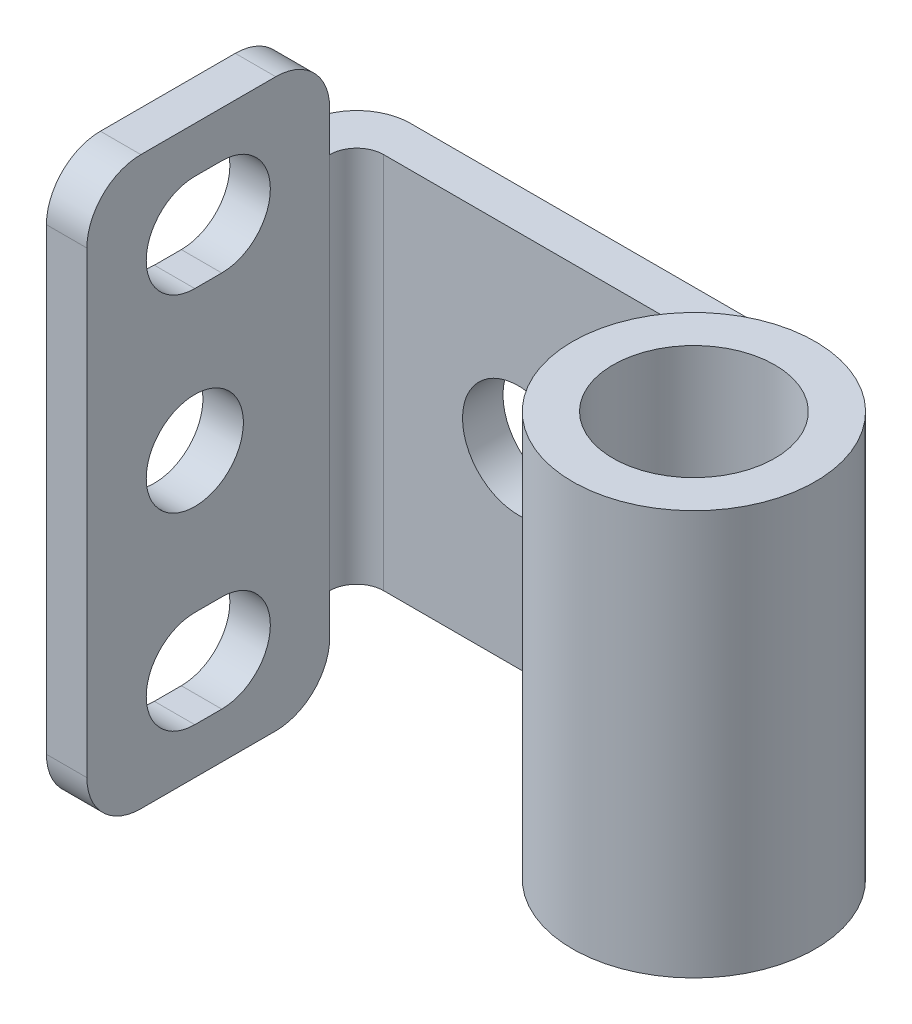
SolidWorks part; units mm, degrees
ref_plane "Спереди" through (0, 0, 0) normal (0, 0, 1) x (1, 0, 0)
ref_plane "Сверху" through (0, 0, 0) normal (0, 1, 0) x (1, 0, 0)
ref_plane "Справа" through (0, 0, 0) normal (1, 0, 0) x (0, 0, -1)
sketch "Эскиз1" plane through (0, 0, 0) normal (0, 0, 1) x (1, 0, 0)
  line L1 (0, 0) -> (11, 0)
  line L2 (0, 0) -> (0, -14)
  line L3 (0, -14) -> (11, -14)
  line L4 (11, 0) -> (11, -14)
  dimension "D1" = 11
  dimension "D2" = 14
base flange "Базовая кромка1" sketch "Эскиз1" thickness 1.5 reverse thickness direction no parameters "D1"=1.7
ref_plane "Плоскость4" through (0, -14.5, 0) normal (0, -1, 0) x (-1, 0, 0)
sketch "Эскиз9" plane through (0, -14.5, 0) normal (0, -1, 0) x (-1, 0, 0)
  line L0 (-4.9522, 1.5) -> (-14.4314, 1.5) construction
  line L1 (0, 1.5) -> (-11, 1.5) construction
  line L2 (-11, 0) -> (-11, -7.4344) construction
  circle A0 centre (-15.5, -3) radius 3
  dimension "D1" = 6
  dimension "D2" = 4.5
  dimension "D3" = 4.5
extrude "Вытянуть-Тонкостенный1" add sketch "Эскиз9" against normal blind 15 separate body thin thin type one direction wall 1.5
sketch "Эскиз10" plane through (11, 0, 0) normal (1, 0, 0) x (0, 0, -1)
  line L0 (0, -14) -> (0, 0) construction
  line L1 (1.5, 0) -> (0, 0)
  line L2 (1.5, 0) -> (1.5, -14)
  line L3 (1.5, -14) -> (0, -14)
  line L4 (0, 0) -> (0, -14)
  line L5 (1.5, -14) -> (0, -14) construction
extrude "Бобышка-Вытянуть1" add sketch "Эскиз10" along normal blind 4.5
sketch "Эскиз11" plane through (0, 0, -1.5) normal (0, 0, -1) x (-1, 0, 0)
  line L1 (0, -14) -> (1.5, -14)
  line L2 (0, -14) -> (0, 0)
  line L3 (0, 0) -> (1.5, 0)
  line L4 (1.5, -14) -> (1.5, 0)
  dimension "D1" = 1.5
extrude "Бобышка-Вытянуть2" add sketch "Эскиз11" against normal blind 11.5
fillet "Скругление2" radius 2 1 edges at (-1.5, -7, -1.5)
fillet "Скругление3" radius 1 1 edges at (0, -7, 0)
sketch "Эскиз12" plane through (-1.5, 0, 0) normal (-1, 0, 0) x (0, 0, 1)
  line L0 (10, -7) -> (-5.3539, -7) construction
  line L1 (10, -14) -> (1, -14)
  line L2 (10, -14) -> (10, -17.5)
  line L3 (10, -17.5) -> (1, -17.5)
  line L4 (1, -14) -> (1, -17.5)
  line L5 (10, -14) -> (10, 0) construction
  line L6 (10, 3.5) -> (1, 3.5)
  line L7 (1, 0) -> (1, 3.5)
  line L8 (10, 0) -> (1, 0)
  line L9 (10, 0) -> (10, 3.5)
  dimension "D1" = 3.5
  dimension "D2" = 9
extrude "Бобышка-Вытянуть3" add sketch "Эскиз12" against normal blind 1.5
fillet "Скругление4" radius 2 4 edges at (-0.75, 3.5, 10) (-0.75, 3.5, 1) (-0.75, -17.5, 1) (-0.75, -17.5, 10)
sketch "Эскиз13" plane through (-1.5, 0, 0) normal (-1, 0, 0) x (0, 0, 1)
  line L0 (5.5, 3.5) -> (5.5, -17.5) construction
  line L1 (8, 3.5) -> (3, 3.5) construction
  line L2 (3, -17.5) -> (8, -17.5) construction
  line L3 (10, -7) -> (0.5, -7) construction
  line L4 (10, -15.5) -> (10, 1.5) construction
  line L5 (0.5, 0) -> (0.5, -14) construction
  line L6 (5, 0) -> (6, 0) construction
  line L7 (5, 1.8) -> (6, 1.8)
  line L8 (5, -1.8) -> (6, -1.8)
  line L9 (5, -14) -> (6, -14) construction
  line L10 (5, -15.8) -> (6, -15.8)
  line L11 (5, -12.2) -> (6, -12.2)
  arc A0 (5, 1.8) -> (5, -1.8) centre (5, 0) ccw
  arc A1 (6, -1.8) -> (6, 1.8) centre (6, 0) ccw
  arc A2 (5, -15.8) -> (5, -12.2) centre (5, -14) cw
  arc A3 (6, -12.2) -> (6, -15.8) centre (6, -14) cw
  circle A4 centre (6, -7) radius 1.8
  point P15 (5.5, 0)
  point P23 (5.5, -14)
  dimension "D2" = 1.8
  dimension "D3" = 3.6
  dimension "D1" = 1
extrude "Вырез-Вытянуть1" cut sketch "Эскиз13" against normal blind 1.5 normal cut yes
sketch "Эскиз14" plane through (0, 0, -1.5) normal (0, 0, -1) x (-1, 0, 0)
  line L0 (-0.5, -7) -> (-15.5, -7) construction
  line L1 (-0.5, -14) -> (-0.5, 0) construction
  line L2 (-15.5, -14) -> (-15.5, 0) construction
  circle A0 centre (-6, -7) radius 2.0766
  point P8 (-7.075, -7.5)
  dimension "D1" = 9.5
extrude "Вырез-Вытянуть2" cut sketch "Эскиз14" against normal blind 1.5 normal cut yes
sketch "Сгиб-Линии1" [suppressed] plane through (0, 0, 0) normal (0, 1, 0) x (1, 0, 0)
sketch "Граничная рамка1" [suppressed] plane through (0, 0, 0) normal (0, 1, 0) x (1, 0, 0)
sheet metal parameters "Листовой металл1" thickness 1.5 parameters "D1"=1.7
flat pattern "Развертка1" [suppressed]
sketch "Сгиб-Линии2" plane through (0, 0, 0) normal (0, 1, 0) x (1, 0, 0)
sketch3d "Граничная рамка2" [suppressed]
  line L0 (-7.5, 0, 0) -> (-7.5, -11, 0) construction
  line L1 (0, 0, 0) -> (0, -11, 0) construction
  line L2 (-7.5, 0, 0) -> (0, 0, 0) construction
  line L3 (-7.5, -11, 0) -> (0, -11, 0) construction
sheet metal parameters "Листовой металл4" thickness 1.5 parameters "D1"=1.7
flat pattern "Развертка1"
sketch "Сгиб-Линии2" plane through (0, 0, 0) normal (0, 0, 1) x (1, 0, 0)
  point P0 (1.3402, 0)
  point P1 (1.3402, -15)
sketch3d "Граничная рамка2" [suppressed]
  line L0 (12.1459, 0, 0) -> (12.1459, -15, 0) construction
  line L1 (0, 0, 0) -> (0, -15, 0) construction
  line L2 (12.1459, 0, 0) -> (0, 0, 0) construction
  line L3 (12.1459, -15, 0) -> (0, -15, 0) construction
sheet metal parameters "Листовой металл5" thickness 1.5 parameters "D1"=1.7
flat pattern "Развертка1"
sketch "Сгиб-Линии2" plane through (0, 0, 0) normal (0, 0, 1) x (1, 0, 0)
sketch3d "Граничная рамка2" [suppressed]
  line L0 (-1.5, -15, 10) -> (20, -15, 10) construction
  line L1 (-1.5, 0, 10) -> (20, 0, 10) construction
  line L2 (-1.5, -15, 10) -> (-1.5, 0, 10) construction
  line L3 (20, -15, 10) -> (20, 0, 10) construction
sheet metal parameters "Листовой металл6" thickness 1.5 parameters "D1"=1.7
flat pattern "Развертка1"
sketch "Сгиб-Линии2" plane through (0, 0, 0) normal (0, 0, 1) x (1, 0, 0)
sketch3d "Граничная рамка2" [suppressed]
  line L0 (20, 3.5, 10) -> (20, -18.5, 10) construction
  line L1 (-1.5, 3.5, 10) -> (-1.5, -18.5, 10) construction
  line L2 (20, 3.5, 10) -> (-1.5, 3.5, 10) construction
  line L3 (20, -18.5, 10) -> (-1.5, -18.5, 10) construction
sheet metal parameters "Листовой металл7" thickness 1.5 parameters "D1"=1.7
flat pattern "Развертка1"
sketch "Сгиб-Линии2" plane through (0, 0, 0) normal (0, 0, 1) x (1, 0, 0)
sketch3d "Граничная рамка2" [suppressed]
  line L0 (20, 3.5, 10) -> (20, -18.5, 10) construction
  line L1 (-1.5, 3.5, 10) -> (-1.5, -18.5, 10) construction
  line L2 (20, 3.5, 10) -> (-1.5, 3.5, 10) construction
  line L3 (20, -18.5, 10) -> (-1.5, -18.5, 10) construction
sheet metal parameters "Листовой металл8" thickness 1.5 parameters "D1"=1.7
flat pattern "Развертка1"
sketch "Сгиб-Линии2" plane through (0, 0, 0) normal (0, 0, 1) x (1, 0, 0)
sketch3d "Граничная рамка2" [suppressed]
  line L0 (-1.5, -17.5, 10) -> (20, -17.5, 10) construction
  line L1 (-1.5, 3.5, 10) -> (20, 3.5, 10) construction
  line L2 (-1.5, -17.5, 10) -> (-1.5, 3.5, 10) construction
  line L3 (20, -17.5, 10) -> (20, 3.5, 10) construction
